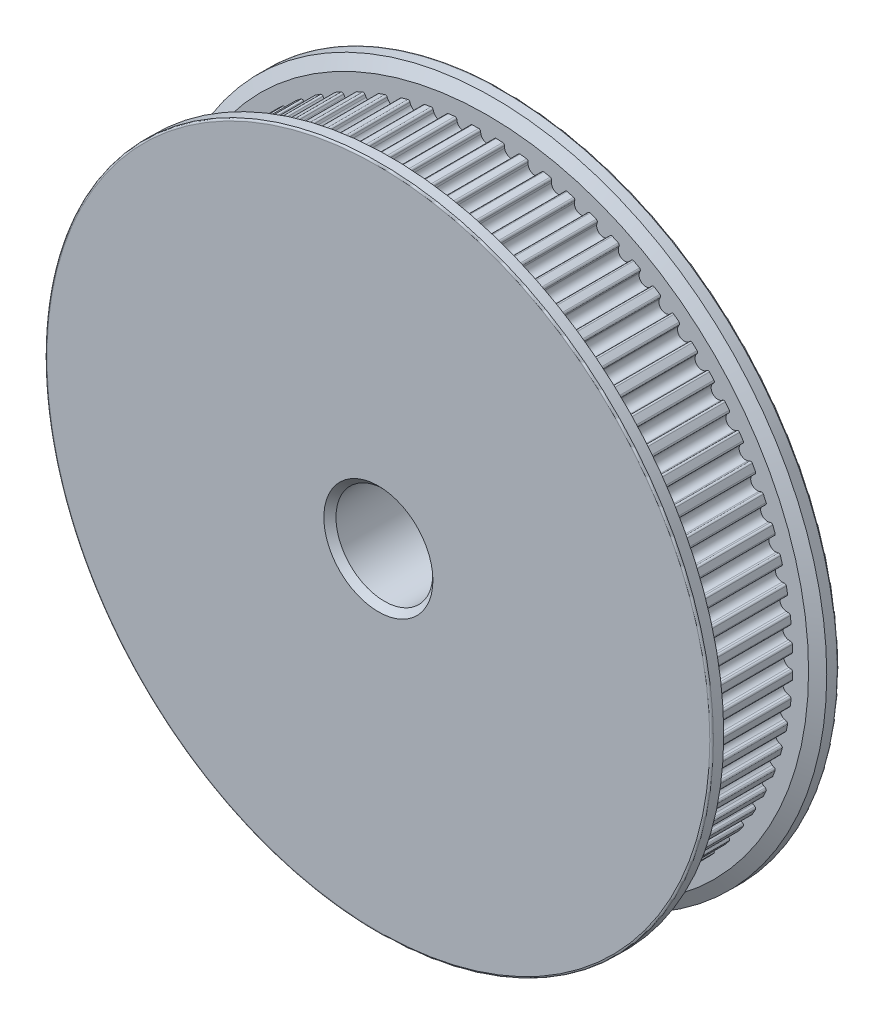
SolidWorks part; units mm, degrees
ref_plane "Front Plane" through (0, 0, 0) normal (0, 0, 1) x (1, 0, 0)
ref_plane "Top Plane" through (0, 0, 0) normal (0, 1, 0) x (1, 0, 0)
ref_plane "Right Plane" through (0, 0, 0) normal (1, 0, 0) x (0, 0, -1)
sketch "Sketch1" plane through (0, 0, 0) normal (0, 0, 1) x (1, 0, 0)
  circle A0 centre (0, 0) radius 19
  dimension "D1" = 38
extrude "Boss-Extrude1" add sketch "Sketch1" along normal blind 10
sketch "Sketch2" plane through (0, 0, 10) normal (0, 0, 1) x (1, 0, 0)
  circle A0 centre (0, 0) radius 27.5
  dimension "D1" = 55
extrude "Boss-Extrude2" add sketch "Sketch2" along normal blind 1.5 contours A0
sketch "Sketch3" plane through (0, 0, 11.5) normal (0, 0, 1) x (1, 0, 0)
  circle A0 centre (0, 0) radius 25.2
  dimension "D1" = 50.4
extrude "Boss-Extrude3" add sketch "Sketch3" along normal blind 7.5
sketch "Sketch4" plane through (0, 0, 19) normal (0, 0, 1) x (1, 0, 0)
  circle A0 centre (0, 0) radius 27.5
extrude "Boss-Extrude4" add sketch "Sketch4" along normal blind 1.5
sketch "Sketch5" plane through (0, 0, 11.5) normal (0, 0, 1) x (1, 0, 0)
  line L0 (0, 0) -> (38.9808, 0) construction
  line L1 (25.1897, 0.7199) -> (25.7855, 0.7199)
  line L2 (25.7855, 0.7199) -> (25.7855, -0.7199)
  line L3 (25.7855, -0.7199) -> (25.1897, -0.7199)
  line L4 (25.1685, -1.2587) -> (25.7625, -1.3054)
  line L5 (25.7625, -1.3054) -> (25.6496, -2.7408)
  line L6 (25.6496, -2.7408) -> (25.0556, -2.694)
  line L7 (24.9922, -3.2295) -> (25.5807, -3.3227)
  line L8 (25.5807, -3.3227) -> (25.3555, -4.7448)
  line L9 (25.3555, -4.7448) -> (24.767, -4.6516)
  line L10 (24.6618, -5.1804) -> (25.2411, -5.3195)
  line L11 (25.2411, -5.3195) -> (24.905, -6.7195)
  line L12 (24.905, -6.7195) -> (24.3257, -6.5804)
  line L13 (24.1793, -7.0994) -> (24.746, -7.2835)
  line L14 (24.746, -7.2835) -> (24.301, -8.6528)
  line L15 (24.301, -8.6528) -> (23.7344, -8.4687)
  line L16 (23.5477, -8.9746) -> (24.0982, -9.2026)
  line L17 (24.0982, -9.2026) -> (23.5472, -10.5328)
  line L18 (23.5472, -10.5328) -> (22.9968, -10.3048)
  line L19 (22.771, -10.7945) -> (23.3019, -11.065)
  line L20 (23.3019, -11.065) -> (22.6483, -12.3478)
  line L21 (22.6483, -12.3478) -> (22.1174, -12.0773)
  line L22 (21.8539, -12.5478) -> (22.3619, -12.8591)
  line L23 (22.3619, -12.8591) -> (21.6096, -14.0867)
  line L24 (21.6096, -14.0867) -> (21.1016, -13.7754)
  line L25 (20.802, -14.2237) -> (21.2841, -14.574)
  line L26 (21.2841, -14.574) -> (20.4378, -15.7388)
  line L27 (20.4378, -15.7388) -> (19.9558, -15.3885)
  line L28 (19.6219, -15.812) -> (20.075, -16.199)
  line L29 (20.075, -16.199) -> (19.1399, -17.2938)
  line L30 (19.1399, -17.2938) -> (18.6869, -16.9068)
  line L31 (18.3209, -17.3028) -> (18.7422, -17.7241)
  line L32 (18.7422, -17.7241) -> (17.7241, -18.7422)
  line L33 (17.7241, -18.7422) -> (17.3028, -18.3209)
  line L34 (16.9068, -18.6869) -> (17.2938, -19.1399)
  line L35 (17.2938, -19.1399) -> (16.199, -20.075)
  line L36 (16.199, -20.075) -> (15.812, -19.6219)
  line L37 (15.3885, -19.9558) -> (15.7388, -20.4378)
  line L38 (15.7388, -20.4378) -> (14.574, -21.2841)
  line L39 (14.574, -21.2841) -> (14.2237, -20.802)
  line L40 (13.7754, -21.1016) -> (14.0867, -21.6096)
  line L41 (14.0867, -21.6096) -> (12.8591, -22.3619)
  line L42 (12.8591, -22.3619) -> (12.5478, -21.8539)
  line L43 (12.0773, -22.1174) -> (12.3478, -22.6483)
  line L44 (12.3478, -22.6483) -> (11.065, -23.3019)
  line L45 (11.065, -23.3019) -> (10.7945, -22.771)
  line L46 (10.3048, -22.9968) -> (10.5328, -23.5472)
  line L47 (10.5328, -23.5472) -> (9.2026, -24.0982)
  line L48 (9.2026, -24.0982) -> (8.9746, -23.5477)
  line L49 (8.4687, -23.7344) -> (8.6528, -24.301)
  line L50 (8.6528, -24.301) -> (7.2835, -24.746)
  line L51 (7.2835, -24.746) -> (7.0994, -24.1793)
  line L52 (6.5804, -24.3257) -> (6.7195, -24.905)
  line L53 (6.7195, -24.905) -> (5.3195, -25.2411)
  line L54 (5.3195, -25.2411) -> (5.1804, -24.6618)
  line L55 (4.6516, -24.767) -> (4.7448, -25.3555)
  line L56 (4.7448, -25.3555) -> (3.3227, -25.5807)
  line L57 (3.3227, -25.5807) -> (3.2295, -24.9922)
  line L58 (2.694, -25.0556) -> (2.7408, -25.6496)
  line L59 (2.7408, -25.6496) -> (1.3054, -25.7625)
  line L60 (1.3054, -25.7625) -> (1.2587, -25.1685)
  line L61 (0.7199, -25.1897) -> (0.7199, -25.7855)
  line L62 (0.7199, -25.7855) -> (-0.7199, -25.7855)
  line L63 (-0.7199, -25.7855) -> (-0.7199, -25.1897)
  line L64 (-1.2587, -25.1685) -> (-1.3054, -25.7625)
  line L65 (-1.3054, -25.7625) -> (-2.7408, -25.6496)
  line L66 (-2.7408, -25.6496) -> (-2.694, -25.0556)
  line L67 (-3.2295, -24.9922) -> (-3.3227, -25.5807)
  line L68 (-3.3227, -25.5807) -> (-4.7448, -25.3555)
  line L69 (-4.7448, -25.3555) -> (-4.6516, -24.767)
  line L70 (-5.1804, -24.6618) -> (-5.3195, -25.2411)
  line L71 (-5.3195, -25.2411) -> (-6.7195, -24.905)
  line L72 (-6.7195, -24.905) -> (-6.5804, -24.3257)
  line L73 (-7.0994, -24.1793) -> (-7.2835, -24.746)
  line L74 (-7.2835, -24.746) -> (-8.6528, -24.301)
  line L75 (-8.6528, -24.301) -> (-8.4687, -23.7344)
  line L76 (-8.9746, -23.5477) -> (-9.2026, -24.0982)
  line L77 (-9.2026, -24.0982) -> (-10.5328, -23.5472)
  line L78 (-10.5328, -23.5472) -> (-10.3048, -22.9968)
  line L79 (-10.7945, -22.771) -> (-11.065, -23.3019)
  line L80 (-11.065, -23.3019) -> (-12.3478, -22.6483)
  line L81 (-12.3478, -22.6483) -> (-12.0773, -22.1174)
  line L82 (-12.5478, -21.8539) -> (-12.8591, -22.3619)
  line L83 (-12.8591, -22.3619) -> (-14.0867, -21.6096)
  line L84 (-14.0867, -21.6096) -> (-13.7754, -21.1016)
  line L85 (-14.2237, -20.802) -> (-14.574, -21.2841)
  line L86 (-14.574, -21.2841) -> (-15.7388, -20.4378)
  line L87 (-15.7388, -20.4378) -> (-15.3885, -19.9558)
  line L88 (-15.812, -19.6219) -> (-16.199, -20.075)
  line L89 (-16.199, -20.075) -> (-17.2938, -19.1399)
  line L90 (-17.2938, -19.1399) -> (-16.9068, -18.6869)
  line L91 (-17.3028, -18.3209) -> (-17.7241, -18.7422)
  line L92 (-17.7241, -18.7422) -> (-18.7422, -17.7241)
  line L93 (-18.7422, -17.7241) -> (-18.3209, -17.3028)
  line L94 (-18.6869, -16.9068) -> (-19.1399, -17.2938)
  line L95 (-19.1399, -17.2938) -> (-20.075, -16.199)
  line L96 (-20.075, -16.199) -> (-19.6219, -15.812)
  line L97 (-19.9558, -15.3885) -> (-20.4378, -15.7388)
  line L98 (-20.4378, -15.7388) -> (-21.2841, -14.574)
  line L99 (-21.2841, -14.574) -> (-20.802, -14.2237)
  line L100 (-21.1016, -13.7754) -> (-21.6096, -14.0867)
  line L101 (-21.6096, -14.0867) -> (-22.3619, -12.8591)
  line L102 (-22.3619, -12.8591) -> (-21.8539, -12.5478)
  line L103 (-22.1174, -12.0773) -> (-22.6483, -12.3478)
  line L104 (-22.6483, -12.3478) -> (-23.3019, -11.065)
  line L105 (-23.3019, -11.065) -> (-22.771, -10.7945)
  line L106 (-22.9968, -10.3048) -> (-23.5472, -10.5328)
  line L107 (-23.5472, -10.5328) -> (-24.0982, -9.2026)
  line L108 (-24.0982, -9.2026) -> (-23.5477, -8.9746)
  line L109 (-23.7344, -8.4687) -> (-24.301, -8.6528)
  line L110 (-24.301, -8.6528) -> (-24.746, -7.2835)
  line L111 (-24.746, -7.2835) -> (-24.1793, -7.0994)
  line L112 (-24.3257, -6.5804) -> (-24.905, -6.7195)
  line L113 (-24.905, -6.7195) -> (-25.2411, -5.3195)
  line L114 (-25.2411, -5.3195) -> (-24.6618, -5.1804)
  line L115 (-24.767, -4.6516) -> (-25.3555, -4.7448)
  line L116 (-25.3555, -4.7448) -> (-25.5807, -3.3227)
  line L117 (-25.5807, -3.3227) -> (-24.9922, -3.2295)
  line L118 (-25.0556, -2.694) -> (-25.6496, -2.7408)
  line L119 (-25.6496, -2.7408) -> (-25.7625, -1.3054)
  line L120 (-25.7625, -1.3054) -> (-25.1685, -1.2587)
  line L121 (-25.1897, -0.7199) -> (-25.7855, -0.7199)
  line L122 (-25.7855, -0.7199) -> (-25.7855, 0.7199)
  line L123 (-25.7855, 0.7199) -> (-25.1897, 0.7199)
  line L124 (-25.1685, 1.2587) -> (-25.7625, 1.3054)
  line L125 (-25.7625, 1.3054) -> (-25.6496, 2.7408)
  line L126 (-25.6496, 2.7408) -> (-25.0556, 2.694)
  line L127 (-24.9922, 3.2295) -> (-25.5807, 3.3227)
  line L128 (-25.5807, 3.3227) -> (-25.3555, 4.7448)
  line L129 (-25.3555, 4.7448) -> (-24.767, 4.6516)
  line L130 (-24.6618, 5.1804) -> (-25.2411, 5.3195)
  line L131 (-25.2411, 5.3195) -> (-24.905, 6.7195)
  line L132 (-24.905, 6.7195) -> (-24.3257, 6.5804)
  line L133 (-24.1793, 7.0994) -> (-24.746, 7.2835)
  line L134 (-24.746, 7.2835) -> (-24.301, 8.6528)
  line L135 (-24.301, 8.6528) -> (-23.7344, 8.4687)
  line L136 (-23.5477, 8.9746) -> (-24.0982, 9.2026)
  line L137 (-24.0982, 9.2026) -> (-23.5472, 10.5328)
  line L138 (-23.5472, 10.5328) -> (-22.9968, 10.3048)
  line L139 (-22.771, 10.7945) -> (-23.3019, 11.065)
  line L140 (-23.3019, 11.065) -> (-22.6483, 12.3478)
  line L141 (-22.6483, 12.3478) -> (-22.1174, 12.0773)
  line L142 (-21.8539, 12.5478) -> (-22.3619, 12.8591)
  line L143 (-22.3619, 12.8591) -> (-21.6096, 14.0867)
  line L144 (-21.6096, 14.0867) -> (-21.1016, 13.7754)
  line L145 (-20.802, 14.2237) -> (-21.2841, 14.574)
  line L146 (-21.2841, 14.574) -> (-20.4378, 15.7388)
  line L147 (-20.4378, 15.7388) -> (-19.9558, 15.3885)
  line L148 (-19.6219, 15.812) -> (-20.075, 16.199)
  line L149 (-20.075, 16.199) -> (-19.1399, 17.2938)
  line L150 (-19.1399, 17.2938) -> (-18.6869, 16.9068)
  line L151 (-18.3209, 17.3028) -> (-18.7422, 17.7241)
  line L152 (-18.7422, 17.7241) -> (-17.7241, 18.7422)
  line L153 (-17.7241, 18.7422) -> (-17.3028, 18.3209)
  line L154 (-16.9068, 18.6869) -> (-17.2938, 19.1399)
  line L155 (-17.2938, 19.1399) -> (-16.199, 20.075)
  line L156 (-16.199, 20.075) -> (-15.812, 19.6219)
  line L157 (-15.3885, 19.9558) -> (-15.7388, 20.4378)
  line L158 (-15.7388, 20.4378) -> (-14.574, 21.2841)
  line L159 (-14.574, 21.2841) -> (-14.2237, 20.802)
  line L160 (-13.7754, 21.1016) -> (-14.0867, 21.6096)
  line L161 (-14.0867, 21.6096) -> (-12.8591, 22.3619)
  line L162 (-12.8591, 22.3619) -> (-12.5478, 21.8539)
  line L163 (-12.0773, 22.1174) -> (-12.3478, 22.6483)
  line L164 (-12.3478, 22.6483) -> (-11.065, 23.3019)
  line L165 (-11.065, 23.3019) -> (-10.7945, 22.771)
  line L166 (-10.3048, 22.9968) -> (-10.5328, 23.5472)
  line L167 (-10.5328, 23.5472) -> (-9.2026, 24.0982)
  line L168 (-9.2026, 24.0982) -> (-8.9746, 23.5477)
  line L169 (-8.4687, 23.7344) -> (-8.6528, 24.301)
  line L170 (-8.6528, 24.301) -> (-7.2835, 24.746)
  line L171 (-7.2835, 24.746) -> (-7.0994, 24.1793)
  line L172 (-6.5804, 24.3257) -> (-6.7195, 24.905)
  line L173 (-6.7195, 24.905) -> (-5.3195, 25.2411)
  line L174 (-5.3195, 25.2411) -> (-5.1804, 24.6618)
  line L175 (-4.6516, 24.767) -> (-4.7448, 25.3555)
  line L176 (-4.7448, 25.3555) -> (-3.3227, 25.5807)
  line L177 (-3.3227, 25.5807) -> (-3.2295, 24.9922)
  line L178 (-2.694, 25.0556) -> (-2.7408, 25.6496)
  line L179 (-2.7408, 25.6496) -> (-1.3054, 25.7625)
  line L180 (-1.3054, 25.7625) -> (-1.2587, 25.1685)
  line L181 (-0.7199, 25.1897) -> (-0.7199, 25.7855)
  line L182 (-0.7199, 25.7855) -> (0.7199, 25.7855)
  line L183 (0.7199, 25.7855) -> (0.7199, 25.1897)
  line L184 (1.2587, 25.1685) -> (1.3054, 25.7625)
  line L185 (1.3054, 25.7625) -> (2.7408, 25.6496)
  line L186 (2.7408, 25.6496) -> (2.694, 25.0556)
  line L187 (3.2295, 24.9922) -> (3.3227, 25.5807)
  line L188 (3.3227, 25.5807) -> (4.7448, 25.3555)
  line L189 (4.7448, 25.3555) -> (4.6516, 24.767)
  line L190 (5.1804, 24.6618) -> (5.3195, 25.2411)
  line L191 (5.3195, 25.2411) -> (6.7195, 24.905)
  line L192 (6.7195, 24.905) -> (6.5804, 24.3257)
  line L193 (7.0994, 24.1793) -> (7.2835, 24.746)
  line L194 (7.2835, 24.746) -> (8.6528, 24.301)
  line L195 (8.6528, 24.301) -> (8.4687, 23.7344)
  line L196 (8.9746, 23.5477) -> (9.2026, 24.0982)
  line L197 (9.2026, 24.0982) -> (10.5328, 23.5472)
  line L198 (10.5328, 23.5472) -> (10.3048, 22.9968)
  line L199 (10.7945, 22.771) -> (11.065, 23.3019)
  line L200 (11.065, 23.3019) -> (12.3478, 22.6483)
  line L201 (12.3478, 22.6483) -> (12.0773, 22.1174)
  line L202 (12.5478, 21.8539) -> (12.8591, 22.3619)
  line L203 (12.8591, 22.3619) -> (14.0867, 21.6096)
  line L204 (14.0867, 21.6096) -> (13.7754, 21.1016)
  line L205 (14.2237, 20.802) -> (14.574, 21.2841)
  line L206 (14.574, 21.2841) -> (15.7388, 20.4378)
  line L207 (15.7388, 20.4378) -> (15.3885, 19.9558)
  line L208 (15.812, 19.6219) -> (16.199, 20.075)
  line L209 (16.199, 20.075) -> (17.2938, 19.1399)
  line L210 (17.2938, 19.1399) -> (16.9068, 18.6869)
  line L211 (17.3028, 18.3209) -> (17.7241, 18.7422)
  line L212 (17.7241, 18.7422) -> (18.7422, 17.7241)
  line L213 (18.7422, 17.7241) -> (18.3209, 17.3028)
  line L214 (18.6869, 16.9068) -> (19.1399, 17.2938)
  line L215 (19.1399, 17.2938) -> (20.075, 16.199)
  line L216 (20.075, 16.199) -> (19.6219, 15.812)
  line L217 (19.9558, 15.3885) -> (20.4378, 15.7388)
  line L218 (20.4378, 15.7388) -> (21.2841, 14.574)
  line L219 (21.2841, 14.574) -> (20.802, 14.2237)
  line L220 (21.1016, 13.7754) -> (21.6096, 14.0867)
  line L221 (21.6096, 14.0867) -> (22.3619, 12.8591)
  line L222 (22.3619, 12.8591) -> (21.8539, 12.5478)
  line L223 (22.1174, 12.0773) -> (22.6483, 12.3478)
  line L224 (22.6483, 12.3478) -> (23.3019, 11.065)
  line L225 (23.3019, 11.065) -> (22.771, 10.7945)
  line L226 (22.9968, 10.3048) -> (23.5472, 10.5328)
  line L227 (23.5472, 10.5328) -> (24.0982, 9.2026)
  line L228 (24.0982, 9.2026) -> (23.5477, 8.9746)
  line L229 (23.7344, 8.4687) -> (24.301, 8.6528)
  line L230 (24.301, 8.6528) -> (24.746, 7.2835)
  line L231 (24.746, 7.2835) -> (24.1793, 7.0994)
  line L232 (24.3257, 6.5804) -> (24.905, 6.7195)
  line L233 (24.905, 6.7195) -> (25.2411, 5.3195)
  line L234 (25.2411, 5.3195) -> (24.6618, 5.1804)
  line L235 (24.767, 4.6516) -> (25.3555, 4.7448)
  line L236 (25.3555, 4.7448) -> (25.5807, 3.3227)
  line L237 (25.5807, 3.3227) -> (24.9922, 3.2295)
  line L238 (25.0556, 2.694) -> (25.6496, 2.7408)
  line L239 (25.6496, 2.7408) -> (25.7625, 1.3054)
  line L240 (25.7625, 1.3054) -> (25.1685, 1.2587)
  circle A0 centre (0, 0) radius 25.45 construction
  circle A1 centre (0, 0) radius 25.2 construction
  arc A2 (24.8691, 0.5381) -> (24.8691, -0.5381) centre (25.005, 0) ccw
  arc A4 (24.8346, -1.4148) -> (24.7502, -2.4876) centre (24.9279, -1.9619) ccw
  arc A5 (25.0159, -1.4012) -> (25.1685, -1.2587) centre (25.0187, -1.2512) ccw
  arc A6 (25.0487, 0.5659) -> (25.1897, 0.7199) centre (25.0398, 0.7156) ccw
  arc A7 (25.0487, -0.5659) -> (25.1897, -0.7199) centre (25.0398, -0.7156) cw
  arc A8 (25.0487, 0.5659) -> (24.8691, 0.5381) centre (25.106, -0.4) ccw
  arc A9 (25.0487, -0.5659) -> (24.8691, -0.5381) centre (25.106, 0.4) cw
  arc A10 (24.9271, -2.5294) -> (25.0556, -2.694) centre (24.9064, -2.678) cw
  arc A11 (25.0159, -1.4012) -> (24.8346, -1.4148) centre (24.9973, -2.3686) ccw
  arc A12 (24.9271, -2.5294) -> (24.7502, -2.4876) centre (25.06, -1.571) cw
  circle A13 centre (0, 0) radius 25.45 construction
  circle A14 centre (0, 0) radius 25.2 construction
  arc A15 (24.6471, -3.3589) -> (24.4787, -4.4219) centre (24.6971, -3.9116) ccw
  arc A16 (24.8288, -3.3596) -> (24.9922, -3.2295) centre (24.8434, -3.2103) ccw
  arc A17 (24.6518, -4.4774) -> (24.767, -4.6516) centre (24.6196, -4.6239) cw
  arc A18 (24.8288, -3.3596) -> (24.6471, -3.3589) centre (24.7344, -4.3225) ccw
  arc A19 (24.6518, -4.4774) -> (24.4787, -4.4219) centre (24.8595, -3.5324) cw
  circle A20 centre (0, 0) radius 25.45 construction
  circle A21 centre (0, 0) radius 25.2 construction
  arc A22 (24.3076, -5.2823) -> (24.0563, -6.3288) centre (24.3141, -5.8373) ccw
  arc A23 (24.4887, -5.2973) -> (24.6618, -5.1804) centre (24.515, -5.1496) ccw
  arc A24 (24.2245, -6.3977) -> (24.3257, -6.5804) centre (24.1809, -6.5412) cw
  arc A25 (24.4887, -5.2973) -> (24.3076, -5.2823) centre (24.319, -6.2498) ccw
  arc A26 (24.2245, -6.3977) -> (24.0563, -6.3288) centre (24.5057, -5.4719) cw
  circle A27 centre (0, 0) radius 25.45 construction
  circle A28 centre (0, 0) radius 25.2 construction
  arc A29 (23.8182, -7.1732) -> (23.4856, -8.1967) centre (23.7812, -7.727) ccw
  arc A30 (23.9976, -7.2023) -> (24.1793, -7.0994) centre (24.0354, -7.0571) ccw
  arc A31 (23.6478, -8.2786) -> (23.7344, -8.4687) centre (23.5931, -8.4183) cw
  arc A32 (23.9976, -7.2023) -> (23.8182, -7.1732) centre (23.7537, -8.1386) ccw
  arc A33 (23.6478, -8.2786) -> (23.4856, -8.1967) centre (24.0009, -7.3778) cw
  circle A34 centre (0, 0) radius 25.45 construction
  circle A35 centre (0, 0) radius 25.2 construction
  arc A36 (23.182, -9.0198) -> (22.7701, -10.0141) centre (23.1016, -9.569) ccw
  arc A37 (23.3585, -9.0629) -> (23.5477, -8.9746) centre (23.4076, -8.9212) ccw
  arc A38 (22.9254, -10.1085) -> (22.9968, -10.3048) centre (22.8599, -10.2434) cw
  arc A39 (23.3585, -9.0629) -> (23.182, -9.0198) centre (23.0419, -9.9772) ccw
  arc A40 (22.9254, -10.1085) -> (22.7701, -10.0141) centre (23.348, -9.2381) cw
  circle A41 centre (0, 0) radius 25.45 construction
  circle A42 centre (0, 0) radius 25.2 construction
  arc A43 (22.4028, -10.8109) -> (21.9142, -11.7698) centre (22.2796, -11.352) ccw
  arc A44 (22.5754, -10.8677) -> (22.771, -10.7945) centre (22.6355, -10.7302) ccw
  arc A45 (22.0616, -11.876) -> (22.1174, -12.0773) centre (21.9857, -12.0054) cw
  arc A46 (22.5754, -10.8677) -> (22.4028, -10.8109) centre (22.188, -11.7543) ccw
  arc A47 (22.0616, -11.876) -> (21.9142, -11.7698) centre (22.5512, -11.0415) cw
  circle A48 centre (0, 0) radius 25.45 construction
  circle A49 centre (0, 0) radius 25.2 construction
  arc A50 (21.4855, -12.5353) -> (20.9232, -13.4529) centre (21.3203, -13.0651) ccw
  arc A51 (21.6532, -12.6054) -> (21.8539, -12.5478) centre (21.7238, -12.4731) ccw
  arc A52 (21.0618, -13.5704) -> (21.1016, -13.7754) centre (20.976, -13.6934) cw
  arc A53 (21.6532, -12.6054) -> (21.4855, -12.5353) centre (21.1974, -13.4589) ccw
  arc A54 (21.0618, -13.5704) -> (20.9232, -13.4529) centre (21.6154, -12.7768) cw
  circle A55 centre (0, 0) radius 25.45 construction
  circle A56 centre (0, 0) radius 25.2 construction
  arc A57 (20.4358, -14.1823) -> (19.8032, -15.053) centre (20.2295, -14.6976) ccw
  arc A58 (20.5974, -14.2654) -> (20.802, -14.2237) centre (20.6782, -14.1391) ccw
  arc A59 (19.9322, -15.181) -> (19.9558, -15.3885) centre (19.837, -15.2969) cw
  arc A60 (20.5974, -14.2654) -> (20.4358, -14.1823) centre (20.0761, -15.0806) ccw
  arc A61 (19.9322, -15.181) -> (19.8032, -15.053) centre (20.5463, -14.4334) cw
  circle A62 centre (0, 0) radius 25.45 construction
  circle A63 centre (0, 0) radius 25.2 construction
  arc A64 (19.2601, -15.742) -> (18.5611, -16.5603) centre (19.014, -16.2394) ccw
  arc A65 (19.4147, -15.8375) -> (19.6219, -15.812) centre (19.5051, -15.7179) ccw
  arc A66 (18.6797, -16.6981) -> (18.6869, -16.9068) centre (18.5757, -16.8062) cw
  arc A67 (19.4147, -15.8375) -> (19.2601, -15.742) centre (18.831, -16.6092) ccw
  arc A68 (18.6797, -16.6981) -> (18.5611, -16.5603) centre (19.3506, -16.0009) cw
  circle A69 centre (0, 0) radius 25.45 construction
  circle A70 centre (0, 0) radius 25.2 construction
  arc A71 (17.9656, -17.2046) -> (17.2046, -17.9656) centre (17.6812, -17.6812) ccw
  arc A72 (18.1122, -17.312) -> (18.3209, -17.3028) centre (18.2118, -17.1998) ccw
  arc A73 (17.312, -18.1122) -> (17.3028, -18.3209) centre (17.1998, -18.2118) cw
  arc A74 (18.1122, -17.312) -> (17.9656, -17.2046) centre (17.4698, -18.0355) ccw
  arc A75 (17.312, -18.1122) -> (17.2046, -17.9656) centre (18.0355, -17.4698) cw
  circle A76 centre (0, 0) radius 25.45 construction
  circle A77 centre (0, 0) radius 25.2 construction
  arc A78 (16.5603, -18.5611) -> (15.742, -19.2601) centre (16.2394, -19.014) ccw
  arc A79 (16.6981, -18.6797) -> (16.9068, -18.6869) centre (16.8062, -18.5757) ccw
  arc A80 (15.8375, -19.4147) -> (15.812, -19.6219) centre (15.7179, -19.5051) cw
  arc A81 (16.6981, -18.6797) -> (16.5603, -18.5611) centre (16.0009, -19.3506) ccw
  arc A82 (15.8375, -19.4147) -> (15.742, -19.2601) centre (16.6092, -18.831) cw
  circle A83 centre (0, 0) radius 25.45 construction
  circle A84 centre (0, 0) radius 25.2 construction
  arc A85 (15.053, -19.8032) -> (14.1823, -20.4358) centre (14.6976, -20.2295) ccw
  arc A86 (15.181, -19.9322) -> (15.3885, -19.9558) centre (15.2969, -19.837) ccw
  arc A87 (14.2654, -20.5974) -> (14.2237, -20.802) centre (14.1391, -20.6782) cw
  arc A88 (15.181, -19.9322) -> (15.053, -19.8032) centre (14.4334, -20.5463) ccw
  arc A89 (14.2654, -20.5974) -> (14.1823, -20.4358) centre (15.0806, -20.0761) cw
  circle A90 centre (0, 0) radius 25.45 construction
  circle A91 centre (0, 0) radius 25.2 construction
  arc A92 (13.4529, -20.9232) -> (12.5353, -21.4855) centre (13.0651, -21.3203) ccw
  arc A93 (13.5704, -21.0618) -> (13.7754, -21.1016) centre (13.6934, -20.976) ccw
  arc A94 (12.6054, -21.6532) -> (12.5478, -21.8539) centre (12.4731, -21.7238) cw
  arc A95 (13.5704, -21.0618) -> (13.4529, -20.9232) centre (12.7768, -21.6154) ccw
  arc A96 (12.6054, -21.6532) -> (12.5353, -21.4855) centre (13.4589, -21.1974) cw
  circle A97 centre (0, 0) radius 25.45 construction
  circle A98 centre (0, 0) radius 25.2 construction
  arc A99 (11.7698, -21.9142) -> (10.8109, -22.4028) centre (11.352, -22.2796) ccw
  arc A100 (11.876, -22.0616) -> (12.0773, -22.1174) centre (12.0054, -21.9857) ccw
  arc A101 (10.8677, -22.5754) -> (10.7945, -22.771) centre (10.7302, -22.6355) cw
  arc A102 (11.876, -22.0616) -> (11.7698, -21.9142) centre (11.0415, -22.5512) ccw
  arc A103 (10.8677, -22.5754) -> (10.8109, -22.4028) centre (11.7543, -22.188) cw
  circle A104 centre (0, 0) radius 25.45 construction
  circle A105 centre (0, 0) radius 25.2 construction
  arc A106 (10.0141, -22.7701) -> (9.0198, -23.182) centre (9.569, -23.1016) ccw
  arc A107 (10.1085, -22.9254) -> (10.3048, -22.9968) centre (10.2434, -22.8599) ccw
  arc A108 (9.0629, -23.3585) -> (8.9746, -23.5477) centre (8.9212, -23.4076) cw
  arc A109 (10.1085, -22.9254) -> (10.0141, -22.7701) centre (9.2381, -23.348) ccw
  arc A110 (9.0629, -23.3585) -> (9.0198, -23.182) centre (9.9772, -23.0419) cw
  circle A111 centre (0, 0) radius 25.45 construction
  circle A112 centre (0, 0) radius 25.2 construction
  arc A113 (8.1967, -23.4856) -> (7.1732, -23.8182) centre (7.727, -23.7812) ccw
  arc A114 (8.2786, -23.6478) -> (8.4687, -23.7344) centre (8.4183, -23.5931) ccw
  arc A115 (7.2023, -23.9976) -> (7.0994, -24.1793) centre (7.0571, -24.0354) cw
  arc A116 (8.2786, -23.6478) -> (8.1967, -23.4856) centre (7.3778, -24.0009) ccw
  arc A117 (7.2023, -23.9976) -> (7.1732, -23.8182) centre (8.1386, -23.7537) cw
  circle A118 centre (0, 0) radius 25.45 construction
  circle A119 centre (0, 0) radius 25.2 construction
  arc A120 (6.3288, -24.0563) -> (5.2823, -24.3076) centre (5.8373, -24.3141) ccw
  arc A121 (6.3977, -24.2245) -> (6.5804, -24.3257) centre (6.5412, -24.1809) ccw
  arc A122 (5.2973, -24.4887) -> (5.1804, -24.6618) centre (5.1496, -24.515) cw
  arc A123 (6.3977, -24.2245) -> (6.3288, -24.0563) centre (5.4719, -24.5057) ccw
  arc A124 (5.2973, -24.4887) -> (5.2823, -24.3076) centre (6.2498, -24.319) cw
  circle A125 centre (0, 0) radius 25.45 construction
  circle A126 centre (0, 0) radius 25.2 construction
  arc A127 (4.4219, -24.4787) -> (3.3589, -24.6471) centre (3.9116, -24.6971) ccw
  arc A128 (4.4774, -24.6518) -> (4.6516, -24.767) centre (4.6239, -24.6196) ccw
  arc A129 (3.3596, -24.8288) -> (3.2295, -24.9922) centre (3.2103, -24.8434) cw
  arc A130 (4.4774, -24.6518) -> (4.4219, -24.4787) centre (3.5324, -24.8595) ccw
  arc A131 (3.3596, -24.8288) -> (3.3589, -24.6471) centre (4.3225, -24.7344) cw
  circle A132 centre (0, 0) radius 25.45 construction
  circle A133 centre (0, 0) radius 25.2 construction
  arc A134 (2.4876, -24.7502) -> (1.4148, -24.8346) centre (1.9619, -24.9279) ccw
  arc A135 (2.5294, -24.9271) -> (2.694, -25.0556) centre (2.678, -24.9064) ccw
  arc A136 (1.4012, -25.0159) -> (1.2587, -25.1685) centre (1.2512, -25.0187) cw
  arc A137 (2.5294, -24.9271) -> (2.4876, -24.7502) centre (1.571, -25.06) ccw
  arc A138 (1.4012, -25.0159) -> (1.4148, -24.8346) centre (2.3686, -24.9973) cw
  circle A139 centre (0, 0) radius 25.45 construction
  circle A140 centre (0, 0) radius 25.2 construction
  arc A141 (0.5381, -24.8691) -> (-0.5381, -24.8691) centre (0, -25.005) ccw
  arc A142 (0.5659, -25.0487) -> (0.7199, -25.1897) centre (0.7156, -25.0398) ccw
  arc A143 (-0.5659, -25.0487) -> (-0.7199, -25.1897) centre (-0.7156, -25.0398) cw
  arc A144 (0.5659, -25.0487) -> (0.5381, -24.8691) centre (-0.4, -25.106) ccw
  arc A145 (-0.5659, -25.0487) -> (-0.5381, -24.8691) centre (0.4, -25.106) cw
  circle A146 centre (0, 0) radius 25.45 construction
  circle A147 centre (0, 0) radius 25.2 construction
  arc A148 (-1.4148, -24.8346) -> (-2.4876, -24.7502) centre (-1.9619, -24.9279) ccw
  arc A149 (-1.4012, -25.0159) -> (-1.2587, -25.1685) centre (-1.2512, -25.0187) ccw
  arc A150 (-2.5294, -24.9271) -> (-2.694, -25.0556) centre (-2.678, -24.9064) cw
  arc A151 (-1.4012, -25.0159) -> (-1.4148, -24.8346) centre (-2.3686, -24.9973) ccw
  arc A152 (-2.5294, -24.9271) -> (-2.4876, -24.7502) centre (-1.571, -25.06) cw
  circle A153 centre (0, 0) radius 25.45 construction
  circle A154 centre (0, 0) radius 25.2 construction
  arc A155 (-3.3589, -24.6471) -> (-4.4219, -24.4787) centre (-3.9116, -24.6971) ccw
  arc A156 (-3.3596, -24.8288) -> (-3.2295, -24.9922) centre (-3.2103, -24.8434) ccw
  arc A157 (-4.4774, -24.6518) -> (-4.6516, -24.767) centre (-4.6239, -24.6196) cw
  arc A158 (-3.3596, -24.8288) -> (-3.3589, -24.6471) centre (-4.3225, -24.7344) ccw
  arc A159 (-4.4774, -24.6518) -> (-4.4219, -24.4787) centre (-3.5324, -24.8595) cw
  circle A160 centre (0, 0) radius 25.45 construction
  circle A161 centre (0, 0) radius 25.2 construction
  arc A162 (-5.2823, -24.3076) -> (-6.3288, -24.0563) centre (-5.8373, -24.3141) ccw
  arc A163 (-5.2973, -24.4887) -> (-5.1804, -24.6618) centre (-5.1496, -24.515) ccw
  arc A164 (-6.3977, -24.2245) -> (-6.5804, -24.3257) centre (-6.5412, -24.1809) cw
  arc A165 (-5.2973, -24.4887) -> (-5.2823, -24.3076) centre (-6.2498, -24.319) ccw
  arc A166 (-6.3977, -24.2245) -> (-6.3288, -24.0563) centre (-5.4719, -24.5057) cw
  circle A167 centre (0, 0) radius 25.45 construction
  circle A168 centre (0, 0) radius 25.2 construction
  arc A169 (-7.1732, -23.8182) -> (-8.1967, -23.4856) centre (-7.727, -23.7812) ccw
  arc A170 (-7.2023, -23.9976) -> (-7.0994, -24.1793) centre (-7.0571, -24.0354) ccw
  arc A171 (-8.2786, -23.6478) -> (-8.4687, -23.7344) centre (-8.4183, -23.5931) cw
  arc A172 (-7.2023, -23.9976) -> (-7.1732, -23.8182) centre (-8.1386, -23.7537) ccw
  arc A173 (-8.2786, -23.6478) -> (-8.1967, -23.4856) centre (-7.3778, -24.0009) cw
  circle A174 centre (0, 0) radius 25.45 construction
  circle A175 centre (0, 0) radius 25.2 construction
  arc A176 (-9.0198, -23.182) -> (-10.0141, -22.7701) centre (-9.569, -23.1016) ccw
  arc A177 (-9.0629, -23.3585) -> (-8.9746, -23.5477) centre (-8.9212, -23.4076) ccw
  arc A178 (-10.1085, -22.9254) -> (-10.3048, -22.9968) centre (-10.2434, -22.8599) cw
  arc A179 (-9.0629, -23.3585) -> (-9.0198, -23.182) centre (-9.9772, -23.0419) ccw
  arc A180 (-10.1085, -22.9254) -> (-10.0141, -22.7701) centre (-9.2381, -23.348) cw
  circle A181 centre (0, 0) radius 25.45 construction
  circle A182 centre (0, 0) radius 25.2 construction
  arc A183 (-10.8109, -22.4028) -> (-11.7698, -21.9142) centre (-11.352, -22.2796) ccw
  arc A184 (-10.8677, -22.5754) -> (-10.7945, -22.771) centre (-10.7302, -22.6355) ccw
  arc A185 (-11.876, -22.0616) -> (-12.0773, -22.1174) centre (-12.0054, -21.9857) cw
  arc A186 (-10.8677, -22.5754) -> (-10.8109, -22.4028) centre (-11.7543, -22.188) ccw
  arc A187 (-11.876, -22.0616) -> (-11.7698, -21.9142) centre (-11.0415, -22.5512) cw
  circle A188 centre (0, 0) radius 25.45 construction
  circle A189 centre (0, 0) radius 25.2 construction
  arc A190 (-12.5353, -21.4855) -> (-13.4529, -20.9232) centre (-13.0651, -21.3203) ccw
  arc A191 (-12.6054, -21.6532) -> (-12.5478, -21.8539) centre (-12.4731, -21.7238) ccw
  arc A192 (-13.5704, -21.0618) -> (-13.7754, -21.1016) centre (-13.6934, -20.976) cw
  arc A193 (-12.6054, -21.6532) -> (-12.5353, -21.4855) centre (-13.4589, -21.1974) ccw
  arc A194 (-13.5704, -21.0618) -> (-13.4529, -20.9232) centre (-12.7768, -21.6154) cw
  circle A195 centre (0, 0) radius 25.45 construction
  circle A196 centre (0, 0) radius 25.2 construction
  arc A197 (-14.1823, -20.4358) -> (-15.053, -19.8032) centre (-14.6976, -20.2295) ccw
  arc A198 (-14.2654, -20.5974) -> (-14.2237, -20.802) centre (-14.1391, -20.6782) ccw
  arc A199 (-15.181, -19.9322) -> (-15.3885, -19.9558) centre (-15.2969, -19.837) cw
  arc A200 (-14.2654, -20.5974) -> (-14.1823, -20.4358) centre (-15.0806, -20.0761) ccw
  arc A201 (-15.181, -19.9322) -> (-15.053, -19.8032) centre (-14.4334, -20.5463) cw
  circle A202 centre (0, 0) radius 25.45 construction
  circle A203 centre (0, 0) radius 25.2 construction
  arc A204 (-15.742, -19.2601) -> (-16.5603, -18.5611) centre (-16.2394, -19.014) ccw
  arc A205 (-15.8375, -19.4147) -> (-15.812, -19.6219) centre (-15.7179, -19.5051) ccw
  arc A206 (-16.6981, -18.6797) -> (-16.9068, -18.6869) centre (-16.8062, -18.5757) cw
  arc A207 (-15.8375, -19.4147) -> (-15.742, -19.2601) centre (-16.6092, -18.831) ccw
  arc A208 (-16.6981, -18.6797) -> (-16.5603, -18.5611) centre (-16.0009, -19.3506) cw
  circle A209 centre (0, 0) radius 25.45 construction
  circle A210 centre (0, 0) radius 25.2 construction
  arc A211 (-17.2046, -17.9656) -> (-17.9656, -17.2046) centre (-17.6812, -17.6812) ccw
  arc A212 (-17.312, -18.1122) -> (-17.3028, -18.3209) centre (-17.1998, -18.2118) ccw
  arc A213 (-18.1122, -17.312) -> (-18.3209, -17.3028) centre (-18.2118, -17.1998) cw
  arc A214 (-17.312, -18.1122) -> (-17.2046, -17.9656) centre (-18.0355, -17.4698) ccw
  arc A215 (-18.1122, -17.312) -> (-17.9656, -17.2046) centre (-17.4698, -18.0355) cw
  circle A216 centre (0, 0) radius 25.45 construction
  circle A217 centre (0, 0) radius 25.2 construction
  arc A218 (-18.5611, -16.5603) -> (-19.2601, -15.742) centre (-19.014, -16.2394) ccw
  arc A219 (-18.6797, -16.6981) -> (-18.6869, -16.9068) centre (-18.5757, -16.8062) ccw
  arc A220 (-19.4147, -15.8375) -> (-19.6219, -15.812) centre (-19.5051, -15.7179) cw
  arc A221 (-18.6797, -16.6981) -> (-18.5611, -16.5603) centre (-19.3506, -16.0009) ccw
  arc A222 (-19.4147, -15.8375) -> (-19.2601, -15.742) centre (-18.831, -16.6092) cw
  circle A223 centre (0, 0) radius 25.45 construction
  circle A224 centre (0, 0) radius 25.2 construction
  arc A225 (-19.8032, -15.053) -> (-20.4358, -14.1823) centre (-20.2295, -14.6976) ccw
  arc A226 (-19.9322, -15.181) -> (-19.9558, -15.3885) centre (-19.837, -15.2969) ccw
  arc A227 (-20.5974, -14.2654) -> (-20.802, -14.2237) centre (-20.6782, -14.1391) cw
  arc A228 (-19.9322, -15.181) -> (-19.8032, -15.053) centre (-20.5463, -14.4334) ccw
  arc A229 (-20.5974, -14.2654) -> (-20.4358, -14.1823) centre (-20.0761, -15.0806) cw
  circle A230 centre (0, 0) radius 25.45 construction
  circle A231 centre (0, 0) radius 25.2 construction
  arc A232 (-20.9232, -13.4529) -> (-21.4855, -12.5353) centre (-21.3203, -13.0651) ccw
  arc A233 (-21.0618, -13.5704) -> (-21.1016, -13.7754) centre (-20.976, -13.6934) ccw
  arc A234 (-21.6532, -12.6054) -> (-21.8539, -12.5478) centre (-21.7238, -12.4731) cw
  arc A235 (-21.0618, -13.5704) -> (-20.9232, -13.4529) centre (-21.6154, -12.7768) ccw
  arc A236 (-21.6532, -12.6054) -> (-21.4855, -12.5353) centre (-21.1974, -13.4589) cw
  circle A237 centre (0, 0) radius 25.45 construction
  circle A238 centre (0, 0) radius 25.2 construction
  arc A239 (-21.9142, -11.7698) -> (-22.4028, -10.8109) centre (-22.2796, -11.352) ccw
  arc A240 (-22.0616, -11.876) -> (-22.1174, -12.0773) centre (-21.9857, -12.0054) ccw
  arc A241 (-22.5754, -10.8677) -> (-22.771, -10.7945) centre (-22.6355, -10.7302) cw
  arc A242 (-22.0616, -11.876) -> (-21.9142, -11.7698) centre (-22.5512, -11.0415) ccw
  arc A243 (-22.5754, -10.8677) -> (-22.4028, -10.8109) centre (-22.188, -11.7543) cw
  circle A244 centre (0, 0) radius 25.45 construction
  circle A245 centre (0, 0) radius 25.2 construction
  arc A246 (-22.7701, -10.0141) -> (-23.182, -9.0198) centre (-23.1016, -9.569) ccw
  arc A247 (-22.9254, -10.1085) -> (-22.9968, -10.3048) centre (-22.8599, -10.2434) ccw
  arc A248 (-23.3585, -9.0629) -> (-23.5477, -8.9746) centre (-23.4076, -8.9212) cw
  arc A249 (-22.9254, -10.1085) -> (-22.7701, -10.0141) centre (-23.348, -9.2381) ccw
  arc A250 (-23.3585, -9.0629) -> (-23.182, -9.0198) centre (-23.0419, -9.9772) cw
  circle A251 centre (0, 0) radius 25.45 construction
  circle A252 centre (0, 0) radius 25.2 construction
  arc A253 (-23.4856, -8.1967) -> (-23.8182, -7.1732) centre (-23.7812, -7.727) ccw
  arc A254 (-23.6478, -8.2786) -> (-23.7344, -8.4687) centre (-23.5931, -8.4183) ccw
  arc A255 (-23.9976, -7.2023) -> (-24.1793, -7.0994) centre (-24.0354, -7.0571) cw
  arc A256 (-23.6478, -8.2786) -> (-23.4856, -8.1967) centre (-24.0009, -7.3778) ccw
  arc A257 (-23.9976, -7.2023) -> (-23.8182, -7.1732) centre (-23.7537, -8.1386) cw
  circle A258 centre (0, 0) radius 25.45 construction
  circle A259 centre (0, 0) radius 25.2 construction
  arc A260 (-24.0563, -6.3288) -> (-24.3076, -5.2823) centre (-24.3141, -5.8373) ccw
  arc A261 (-24.2245, -6.3977) -> (-24.3257, -6.5804) centre (-24.1809, -6.5412) ccw
  arc A262 (-24.4887, -5.2973) -> (-24.6618, -5.1804) centre (-24.515, -5.1496) cw
  arc A263 (-24.2245, -6.3977) -> (-24.0563, -6.3288) centre (-24.5057, -5.4719) ccw
  arc A264 (-24.4887, -5.2973) -> (-24.3076, -5.2823) centre (-24.319, -6.2498) cw
  circle A265 centre (0, 0) radius 25.45 construction
  circle A266 centre (0, 0) radius 25.2 construction
  arc A267 (-24.4787, -4.4219) -> (-24.6471, -3.3589) centre (-24.6971, -3.9116) ccw
  arc A268 (-24.6518, -4.4774) -> (-24.767, -4.6516) centre (-24.6196, -4.6239) ccw
  arc A269 (-24.8288, -3.3596) -> (-24.9922, -3.2295) centre (-24.8434, -3.2103) cw
  arc A270 (-24.6518, -4.4774) -> (-24.4787, -4.4219) centre (-24.8595, -3.5324) ccw
  arc A271 (-24.8288, -3.3596) -> (-24.6471, -3.3589) centre (-24.7344, -4.3225) cw
  circle A272 centre (0, 0) radius 25.45 construction
  circle A273 centre (0, 0) radius 25.2 construction
  arc A274 (-24.7502, -2.4876) -> (-24.8346, -1.4148) centre (-24.9279, -1.9619) ccw
  arc A275 (-24.9271, -2.5294) -> (-25.0556, -2.694) centre (-24.9064, -2.678) ccw
  arc A276 (-25.0159, -1.4012) -> (-25.1685, -1.2587) centre (-25.0187, -1.2512) cw
  arc A277 (-24.9271, -2.5294) -> (-24.7502, -2.4876) centre (-25.06, -1.571) ccw
  arc A278 (-25.0159, -1.4012) -> (-24.8346, -1.4148) centre (-24.9973, -2.3686) cw
  circle A279 centre (0, 0) radius 25.45 construction
  circle A280 centre (0, 0) radius 25.2 construction
  arc A281 (-24.8691, -0.5381) -> (-24.8691, 0.5381) centre (-25.005, 0) ccw
  arc A282 (-25.0487, -0.5659) -> (-25.1897, -0.7199) centre (-25.0398, -0.7156) ccw
  arc A283 (-25.0487, 0.5659) -> (-25.1897, 0.7199) centre (-25.0398, 0.7156) cw
  arc A284 (-25.0487, -0.5659) -> (-24.8691, -0.5381) centre (-25.106, 0.4) ccw
  arc A285 (-25.0487, 0.5659) -> (-24.8691, 0.5381) centre (-25.106, -0.4) cw
  circle A286 centre (0, 0) radius 25.45 construction
  circle A287 centre (0, 0) radius 25.2 construction
  arc A288 (-24.8346, 1.4148) -> (-24.7502, 2.4876) centre (-24.9279, 1.9619) ccw
  arc A289 (-25.0159, 1.4012) -> (-25.1685, 1.2587) centre (-25.0187, 1.2512) ccw
  arc A290 (-24.9271, 2.5294) -> (-25.0556, 2.694) centre (-24.9064, 2.678) cw
  arc A291 (-25.0159, 1.4012) -> (-24.8346, 1.4148) centre (-24.9973, 2.3686) ccw
  arc A292 (-24.9271, 2.5294) -> (-24.7502, 2.4876) centre (-25.06, 1.571) cw
  circle A293 centre (0, 0) radius 25.45 construction
  circle A294 centre (0, 0) radius 25.2 construction
  arc A295 (-24.6471, 3.3589) -> (-24.4787, 4.4219) centre (-24.6971, 3.9116) ccw
  arc A296 (-24.8288, 3.3596) -> (-24.9922, 3.2295) centre (-24.8434, 3.2103) ccw
  arc A297 (-24.6518, 4.4774) -> (-24.767, 4.6516) centre (-24.6196, 4.6239) cw
  arc A298 (-24.8288, 3.3596) -> (-24.6471, 3.3589) centre (-24.7344, 4.3225) ccw
  arc A299 (-24.6518, 4.4774) -> (-24.4787, 4.4219) centre (-24.8595, 3.5324) cw
  circle A300 centre (0, 0) radius 25.45 construction
  circle A301 centre (0, 0) radius 25.2 construction
  arc A302 (-24.3076, 5.2823) -> (-24.0563, 6.3288) centre (-24.3141, 5.8373) ccw
  arc A303 (-24.4887, 5.2973) -> (-24.6618, 5.1804) centre (-24.515, 5.1496) ccw
  arc A304 (-24.2245, 6.3977) -> (-24.3257, 6.5804) centre (-24.1809, 6.5412) cw
  arc A305 (-24.4887, 5.2973) -> (-24.3076, 5.2823) centre (-24.319, 6.2498) ccw
  arc A306 (-24.2245, 6.3977) -> (-24.0563, 6.3288) centre (-24.5057, 5.4719) cw
  circle A307 centre (0, 0) radius 25.45 construction
  circle A308 centre (0, 0) radius 25.2 construction
  arc A309 (-23.8182, 7.1732) -> (-23.4856, 8.1967) centre (-23.7812, 7.727) ccw
  arc A310 (-23.9976, 7.2023) -> (-24.1793, 7.0994) centre (-24.0354, 7.0571) ccw
  arc A311 (-23.6478, 8.2786) -> (-23.7344, 8.4687) centre (-23.5931, 8.4183) cw
  arc A312 (-23.9976, 7.2023) -> (-23.8182, 7.1732) centre (-23.7537, 8.1386) ccw
  arc A313 (-23.6478, 8.2786) -> (-23.4856, 8.1967) centre (-24.0009, 7.3778) cw
  circle A314 centre (0, 0) radius 25.45 construction
  circle A315 centre (0, 0) radius 25.2 construction
  arc A316 (-23.182, 9.0198) -> (-22.7701, 10.0141) centre (-23.1016, 9.569) ccw
  arc A317 (-23.3585, 9.0629) -> (-23.5477, 8.9746) centre (-23.4076, 8.9212) ccw
  arc A318 (-22.9254, 10.1085) -> (-22.9968, 10.3048) centre (-22.8599, 10.2434) cw
  arc A319 (-23.3585, 9.0629) -> (-23.182, 9.0198) centre (-23.0419, 9.9772) ccw
  arc A320 (-22.9254, 10.1085) -> (-22.7701, 10.0141) centre (-23.348, 9.2381) cw
  circle A321 centre (0, 0) radius 25.45 construction
  circle A322 centre (0, 0) radius 25.2 construction
  arc A323 (-22.4028, 10.8109) -> (-21.9142, 11.7698) centre (-22.2796, 11.352) ccw
  arc A324 (-22.5754, 10.8677) -> (-22.771, 10.7945) centre (-22.6355, 10.7302) ccw
  arc A325 (-22.0616, 11.876) -> (-22.1174, 12.0773) centre (-21.9857, 12.0054) cw
  arc A326 (-22.5754, 10.8677) -> (-22.4028, 10.8109) centre (-22.188, 11.7543) ccw
  arc A327 (-22.0616, 11.876) -> (-21.9142, 11.7698) centre (-22.5512, 11.0415) cw
  circle A328 centre (0, 0) radius 25.45 construction
  circle A329 centre (0, 0) radius 25.2 construction
  arc A330 (-21.4855, 12.5353) -> (-20.9232, 13.4529) centre (-21.3203, 13.0651) ccw
  arc A331 (-21.6532, 12.6054) -> (-21.8539, 12.5478) centre (-21.7238, 12.4731) ccw
  arc A332 (-21.0618, 13.5704) -> (-21.1016, 13.7754) centre (-20.976, 13.6934) cw
  arc A333 (-21.6532, 12.6054) -> (-21.4855, 12.5353) centre (-21.1974, 13.4589) ccw
  arc A334 (-21.0618, 13.5704) -> (-20.9232, 13.4529) centre (-21.6154, 12.7768) cw
  circle A335 centre (0, 0) radius 25.45 construction
  circle A336 centre (0, 0) radius 25.2 construction
  arc A337 (-20.4358, 14.1823) -> (-19.8032, 15.053) centre (-20.2295, 14.6976) ccw
  arc A338 (-20.5974, 14.2654) -> (-20.802, 14.2237) centre (-20.6782, 14.1391) ccw
  arc A339 (-19.9322, 15.181) -> (-19.9558, 15.3885) centre (-19.837, 15.2969) cw
  arc A340 (-20.5974, 14.2654) -> (-20.4358, 14.1823) centre (-20.0761, 15.0806) ccw
  arc A341 (-19.9322, 15.181) -> (-19.8032, 15.053) centre (-20.5463, 14.4334) cw
  circle A342 centre (0, 0) radius 25.45 construction
  circle A343 centre (0, 0) radius 25.2 construction
  arc A344 (-19.2601, 15.742) -> (-18.5611, 16.5603) centre (-19.014, 16.2394) ccw
  arc A345 (-19.4147, 15.8375) -> (-19.6219, 15.812) centre (-19.5051, 15.7179) ccw
  arc A346 (-18.6797, 16.6981) -> (-18.6869, 16.9068) centre (-18.5757, 16.8062) cw
  arc A347 (-19.4147, 15.8375) -> (-19.2601, 15.742) centre (-18.831, 16.6092) ccw
  arc A348 (-18.6797, 16.6981) -> (-18.5611, 16.5603) centre (-19.3506, 16.0009) cw
  circle A349 centre (0, 0) radius 25.45 construction
  circle A350 centre (0, 0) radius 25.2 construction
  arc A351 (-17.9656, 17.2046) -> (-17.2046, 17.9656) centre (-17.6812, 17.6812) ccw
  arc A352 (-18.1122, 17.312) -> (-18.3209, 17.3028) centre (-18.2118, 17.1998) ccw
  arc A353 (-17.312, 18.1122) -> (-17.3028, 18.3209) centre (-17.1998, 18.2118) cw
  arc A354 (-18.1122, 17.312) -> (-17.9656, 17.2046) centre (-17.4698, 18.0355) ccw
  arc A355 (-17.312, 18.1122) -> (-17.2046, 17.9656) centre (-18.0355, 17.4698) cw
  circle A356 centre (0, 0) radius 25.45 construction
  circle A357 centre (0, 0) radius 25.2 construction
  arc A358 (-16.5603, 18.5611) -> (-15.742, 19.2601) centre (-16.2394, 19.014) ccw
  arc A359 (-16.6981, 18.6797) -> (-16.9068, 18.6869) centre (-16.8062, 18.5757) ccw
  arc A360 (-15.8375, 19.4147) -> (-15.812, 19.6219) centre (-15.7179, 19.5051) cw
  arc A361 (-16.6981, 18.6797) -> (-16.5603, 18.5611) centre (-16.0009, 19.3506) ccw
  arc A362 (-15.8375, 19.4147) -> (-15.742, 19.2601) centre (-16.6092, 18.831) cw
  circle A363 centre (0, 0) radius 25.45 construction
  circle A364 centre (0, 0) radius 25.2 construction
  arc A365 (-15.053, 19.8032) -> (-14.1823, 20.4358) centre (-14.6976, 20.2295) ccw
  arc A366 (-15.181, 19.9322) -> (-15.3885, 19.9558) centre (-15.2969, 19.837) ccw
  arc A367 (-14.2654, 20.5974) -> (-14.2237, 20.802) centre (-14.1391, 20.6782) cw
  arc A368 (-15.181, 19.9322) -> (-15.053, 19.8032) centre (-14.4334, 20.5463) ccw
  arc A369 (-14.2654, 20.5974) -> (-14.1823, 20.4358) centre (-15.0806, 20.0761) cw
  circle A370 centre (0, 0) radius 25.45 construction
  circle A371 centre (0, 0) radius 25.2 construction
  arc A372 (-13.4529, 20.9232) -> (-12.5353, 21.4855) centre (-13.0651, 21.3203) ccw
  arc A373 (-13.5704, 21.0618) -> (-13.7754, 21.1016) centre (-13.6934, 20.976) ccw
  arc A374 (-12.6054, 21.6532) -> (-12.5478, 21.8539) centre (-12.4731, 21.7238) cw
  arc A375 (-13.5704, 21.0618) -> (-13.4529, 20.9232) centre (-12.7768, 21.6154) ccw
  arc A376 (-12.6054, 21.6532) -> (-12.5353, 21.4855) centre (-13.4589, 21.1974) cw
  circle A377 centre (0, 0) radius 25.45 construction
  circle A378 centre (0, 0) radius 25.2 construction
  arc A379 (-11.7698, 21.9142) -> (-10.8109, 22.4028) centre (-11.352, 22.2796) ccw
  arc A380 (-11.876, 22.0616) -> (-12.0773, 22.1174) centre (-12.0054, 21.9857) ccw
  arc A381 (-10.8677, 22.5754) -> (-10.7945, 22.771) centre (-10.7302, 22.6355) cw
  arc A382 (-11.876, 22.0616) -> (-11.7698, 21.9142) centre (-11.0415, 22.5512) ccw
  arc A383 (-10.8677, 22.5754) -> (-10.8109, 22.4028) centre (-11.7543, 22.188) cw
  circle A384 centre (0, 0) radius 25.45 construction
  circle A385 centre (0, 0) radius 25.2 construction
  arc A386 (-10.0141, 22.7701) -> (-9.0198, 23.182) centre (-9.569, 23.1016) ccw
  arc A387 (-10.1085, 22.9254) -> (-10.3048, 22.9968) centre (-10.2434, 22.8599) ccw
  arc A388 (-9.0629, 23.3585) -> (-8.9746, 23.5477) centre (-8.9212, 23.4076) cw
  arc A389 (-10.1085, 22.9254) -> (-10.0141, 22.7701) centre (-9.2381, 23.348) ccw
  arc A390 (-9.0629, 23.3585) -> (-9.0198, 23.182) centre (-9.9772, 23.0419) cw
  circle A391 centre (0, 0) radius 25.45 construction
  circle A392 centre (0, 0) radius 25.2 construction
  arc A393 (-8.1967, 23.4856) -> (-7.1732, 23.8182) centre (-7.727, 23.7812) ccw
  arc A394 (-8.2786, 23.6478) -> (-8.4687, 23.7344) centre (-8.4183, 23.5931) ccw
  arc A395 (-7.2023, 23.9976) -> (-7.0994, 24.1793) centre (-7.0571, 24.0354) cw
  arc A396 (-8.2786, 23.6478) -> (-8.1967, 23.4856) centre (-7.3778, 24.0009) ccw
  arc A397 (-7.2023, 23.9976) -> (-7.1732, 23.8182) centre (-8.1386, 23.7537) cw
  circle A398 centre (0, 0) radius 25.45 construction
  circle A399 centre (0, 0) radius 25.2 construction
  arc A400 (-6.3288, 24.0563) -> (-5.2823, 24.3076) centre (-5.8373, 24.3141) ccw
  arc A401 (-6.3977, 24.2245) -> (-6.5804, 24.3257) centre (-6.5412, 24.1809) ccw
  arc A402 (-5.2973, 24.4887) -> (-5.1804, 24.6618) centre (-5.1496, 24.515) cw
  arc A403 (-6.3977, 24.2245) -> (-6.3288, 24.0563) centre (-5.4719, 24.5057) ccw
  arc A404 (-5.2973, 24.4887) -> (-5.2823, 24.3076) centre (-6.2498, 24.319) cw
  circle A405 centre (0, 0) radius 25.45 construction
  circle A406 centre (0, 0) radius 25.2 construction
  arc A407 (-4.4219, 24.4787) -> (-3.3589, 24.6471) centre (-3.9116, 24.6971) ccw
  arc A408 (-4.4774, 24.6518) -> (-4.6516, 24.767) centre (-4.6239, 24.6196) ccw
  arc A409 (-3.3596, 24.8288) -> (-3.2295, 24.9922) centre (-3.2103, 24.8434) cw
  arc A410 (-4.4774, 24.6518) -> (-4.4219, 24.4787) centre (-3.5324, 24.8595) ccw
  arc A411 (-3.3596, 24.8288) -> (-3.3589, 24.6471) centre (-4.3225, 24.7344) cw
  circle A412 centre (0, 0) radius 25.45 construction
  circle A413 centre (0, 0) radius 25.2 construction
  arc A414 (-2.4876, 24.7502) -> (-1.4148, 24.8346) centre (-1.9619, 24.9279) ccw
  arc A415 (-2.5294, 24.9271) -> (-2.694, 25.0556) centre (-2.678, 24.9064) ccw
  arc A416 (-1.4012, 25.0159) -> (-1.2587, 25.1685) centre (-1.2512, 25.0187) cw
  arc A417 (-2.5294, 24.9271) -> (-2.4876, 24.7502) centre (-1.571, 25.06) ccw
  arc A418 (-1.4012, 25.0159) -> (-1.4148, 24.8346) centre (-2.3686, 24.9973) cw
  circle A419 centre (0, 0) radius 25.45 construction
  circle A420 centre (0, 0) radius 25.2 construction
  arc A421 (-0.5381, 24.8691) -> (0.5381, 24.8691) centre (0, 25.005) ccw
  arc A422 (-0.5659, 25.0487) -> (-0.7199, 25.1897) centre (-0.7156, 25.0398) ccw
  arc A423 (0.5659, 25.0487) -> (0.7199, 25.1897) centre (0.7156, 25.0398) cw
  arc A424 (-0.5659, 25.0487) -> (-0.5381, 24.8691) centre (0.4, 25.106) ccw
  arc A425 (0.5659, 25.0487) -> (0.5381, 24.8691) centre (-0.4, 25.106) cw
  circle A426 centre (0, 0) radius 25.45 construction
  circle A427 centre (0, 0) radius 25.2 construction
  arc A428 (1.4148, 24.8346) -> (2.4876, 24.7502) centre (1.9619, 24.9279) ccw
  arc A429 (1.4012, 25.0159) -> (1.2587, 25.1685) centre (1.2512, 25.0187) ccw
  arc A430 (2.5294, 24.9271) -> (2.694, 25.0556) centre (2.678, 24.9064) cw
  arc A431 (1.4012, 25.0159) -> (1.4148, 24.8346) centre (2.3686, 24.9973) ccw
  arc A432 (2.5294, 24.9271) -> (2.4876, 24.7502) centre (1.571, 25.06) cw
  circle A433 centre (0, 0) radius 25.45 construction
  circle A434 centre (0, 0) radius 25.2 construction
  arc A435 (3.3589, 24.6471) -> (4.4219, 24.4787) centre (3.9116, 24.6971) ccw
  arc A436 (3.3596, 24.8288) -> (3.2295, 24.9922) centre (3.2103, 24.8434) ccw
  arc A437 (4.4774, 24.6518) -> (4.6516, 24.767) centre (4.6239, 24.6196) cw
  arc A438 (3.3596, 24.8288) -> (3.3589, 24.6471) centre (4.3225, 24.7344) ccw
  arc A439 (4.4774, 24.6518) -> (4.4219, 24.4787) centre (3.5324, 24.8595) cw
  circle A440 centre (0, 0) radius 25.45 construction
  circle A441 centre (0, 0) radius 25.2 construction
  arc A442 (5.2823, 24.3076) -> (6.3288, 24.0563) centre (5.8373, 24.3141) ccw
  arc A443 (5.2973, 24.4887) -> (5.1804, 24.6618) centre (5.1496, 24.515) ccw
  arc A444 (6.3977, 24.2245) -> (6.5804, 24.3257) centre (6.5412, 24.1809) cw
  arc A445 (5.2973, 24.4887) -> (5.2823, 24.3076) centre (6.2498, 24.319) ccw
  arc A446 (6.3977, 24.2245) -> (6.3288, 24.0563) centre (5.4719, 24.5057) cw
  circle A447 centre (0, 0) radius 25.45 construction
  circle A448 centre (0, 0) radius 25.2 construction
  arc A449 (7.1732, 23.8182) -> (8.1967, 23.4856) centre (7.727, 23.7812) ccw
  arc A450 (7.2023, 23.9976) -> (7.0994, 24.1793) centre (7.0571, 24.0354) ccw
  arc A451 (8.2786, 23.6478) -> (8.4687, 23.7344) centre (8.4183, 23.5931) cw
  arc A452 (7.2023, 23.9976) -> (7.1732, 23.8182) centre (8.1386, 23.7537) ccw
  arc A453 (8.2786, 23.6478) -> (8.1967, 23.4856) centre (7.3778, 24.0009) cw
  circle A454 centre (0, 0) radius 25.45 construction
  circle A455 centre (0, 0) radius 25.2 construction
  arc A456 (9.0198, 23.182) -> (10.0141, 22.7701) centre (9.569, 23.1016) ccw
  arc A457 (9.0629, 23.3585) -> (8.9746, 23.5477) centre (8.9212, 23.4076) ccw
  arc A458 (10.1085, 22.9254) -> (10.3048, 22.9968) centre (10.2434, 22.8599) cw
  arc A459 (9.0629, 23.3585) -> (9.0198, 23.182) centre (9.9772, 23.0419) ccw
  arc A460 (10.1085, 22.9254) -> (10.0141, 22.7701) centre (9.2381, 23.348) cw
  circle A461 centre (0, 0) radius 25.45 construction
  circle A462 centre (0, 0) radius 25.2 construction
  arc A463 (10.8109, 22.4028) -> (11.7698, 21.9142) centre (11.352, 22.2796) ccw
  arc A464 (10.8677, 22.5754) -> (10.7945, 22.771) centre (10.7302, 22.6355) ccw
  arc A465 (11.876, 22.0616) -> (12.0773, 22.1174) centre (12.0054, 21.9857) cw
  arc A466 (10.8677, 22.5754) -> (10.8109, 22.4028) centre (11.7543, 22.188) ccw
  arc A467 (11.876, 22.0616) -> (11.7698, 21.9142) centre (11.0415, 22.5512) cw
  circle A468 centre (0, 0) radius 25.45 construction
  circle A469 centre (0, 0) radius 25.2 construction
  arc A470 (12.5353, 21.4855) -> (13.4529, 20.9232) centre (13.0651, 21.3203) ccw
  arc A471 (12.6054, 21.6532) -> (12.5478, 21.8539) centre (12.4731, 21.7238) ccw
  arc A472 (13.5704, 21.0618) -> (13.7754, 21.1016) centre (13.6934, 20.976) cw
  arc A473 (12.6054, 21.6532) -> (12.5353, 21.4855) centre (13.4589, 21.1974) ccw
  arc A474 (13.5704, 21.0618) -> (13.4529, 20.9232) centre (12.7768, 21.6154) cw
  circle A475 centre (0, 0) radius 25.45 construction
  circle A476 centre (0, 0) radius 25.2 construction
  arc A477 (14.1823, 20.4358) -> (15.053, 19.8032) centre (14.6976, 20.2295) ccw
  arc A478 (14.2654, 20.5974) -> (14.2237, 20.802) centre (14.1391, 20.6782) ccw
  arc A479 (15.181, 19.9322) -> (15.3885, 19.9558) centre (15.2969, 19.837) cw
  arc A480 (14.2654, 20.5974) -> (14.1823, 20.4358) centre (15.0806, 20.0761) ccw
  arc A481 (15.181, 19.9322) -> (15.053, 19.8032) centre (14.4334, 20.5463) cw
  circle A482 centre (0, 0) radius 25.45 construction
  circle A483 centre (0, 0) radius 25.2 construction
  arc A484 (15.742, 19.2601) -> (16.5603, 18.5611) centre (16.2394, 19.014) ccw
  arc A485 (15.8375, 19.4147) -> (15.812, 19.6219) centre (15.7179, 19.5051) ccw
  arc A486 (16.6981, 18.6797) -> (16.9068, 18.6869) centre (16.8062, 18.5757) cw
  arc A487 (15.8375, 19.4147) -> (15.742, 19.2601) centre (16.6092, 18.831) ccw
  arc A488 (16.6981, 18.6797) -> (16.5603, 18.5611) centre (16.0009, 19.3506) cw
  circle A489 centre (0, 0) radius 25.45 construction
  circle A490 centre (0, 0) radius 25.2 construction
  arc A491 (17.2046, 17.9656) -> (17.9656, 17.2046) centre (17.6812, 17.6812) ccw
  arc A492 (17.312, 18.1122) -> (17.3028, 18.3209) centre (17.1998, 18.2118) ccw
  arc A493 (18.1122, 17.312) -> (18.3209, 17.3028) centre (18.2118, 17.1998) cw
  arc A494 (17.312, 18.1122) -> (17.2046, 17.9656) centre (18.0355, 17.4698) ccw
  arc A495 (18.1122, 17.312) -> (17.9656, 17.2046) centre (17.4698, 18.0355) cw
  circle A496 centre (0, 0) radius 25.45 construction
  circle A497 centre (0, 0) radius 25.2 construction
  arc A498 (18.5611, 16.5603) -> (19.2601, 15.742) centre (19.014, 16.2394) ccw
  arc A499 (18.6797, 16.6981) -> (18.6869, 16.9068) centre (18.5757, 16.8062) ccw
  arc A500 (19.4147, 15.8375) -> (19.6219, 15.812) centre (19.5051, 15.7179) cw
  arc A501 (18.6797, 16.6981) -> (18.5611, 16.5603) centre (19.3506, 16.0009) ccw
  arc A502 (19.4147, 15.8375) -> (19.2601, 15.742) centre (18.831, 16.6092) cw
  circle A503 centre (0, 0) radius 25.45 construction
  circle A504 centre (0, 0) radius 25.2 construction
  arc A505 (19.8032, 15.053) -> (20.4358, 14.1823) centre (20.2295, 14.6976) ccw
  arc A506 (19.9322, 15.181) -> (19.9558, 15.3885) centre (19.837, 15.2969) ccw
  arc A507 (20.5974, 14.2654) -> (20.802, 14.2237) centre (20.6782, 14.1391) cw
  arc A508 (19.9322, 15.181) -> (19.8032, 15.053) centre (20.5463, 14.4334) ccw
  arc A509 (20.5974, 14.2654) -> (20.4358, 14.1823) centre (20.0761, 15.0806) cw
  circle A510 centre (0, 0) radius 25.45 construction
  circle A511 centre (0, 0) radius 25.2 construction
  arc A512 (20.9232, 13.4529) -> (21.4855, 12.5353) centre (21.3203, 13.0651) ccw
  arc A513 (21.0618, 13.5704) -> (21.1016, 13.7754) centre (20.976, 13.6934) ccw
  arc A514 (21.6532, 12.6054) -> (21.8539, 12.5478) centre (21.7238, 12.4731) cw
  arc A515 (21.0618, 13.5704) -> (20.9232, 13.4529) centre (21.6154, 12.7768) ccw
  arc A516 (21.6532, 12.6054) -> (21.4855, 12.5353) centre (21.1974, 13.4589) cw
  circle A517 centre (0, 0) radius 25.45 construction
  circle A518 centre (0, 0) radius 25.2 construction
  arc A519 (21.9142, 11.7698) -> (22.4028, 10.8109) centre (22.2796, 11.352) ccw
  arc A520 (22.0616, 11.876) -> (22.1174, 12.0773) centre (21.9857, 12.0054) ccw
  arc A521 (22.5754, 10.8677) -> (22.771, 10.7945) centre (22.6355, 10.7302) cw
  arc A522 (22.0616, 11.876) -> (21.9142, 11.7698) centre (22.5512, 11.0415) ccw
  arc A523 (22.5754, 10.8677) -> (22.4028, 10.8109) centre (22.188, 11.7543) cw
  circle A524 centre (0, 0) radius 25.45 construction
  circle A525 centre (0, 0) radius 25.2 construction
  arc A526 (22.7701, 10.0141) -> (23.182, 9.0198) centre (23.1016, 9.569) ccw
  arc A527 (22.9254, 10.1085) -> (22.9968, 10.3048) centre (22.8599, 10.2434) ccw
  arc A528 (23.3585, 9.0629) -> (23.5477, 8.9746) centre (23.4076, 8.9212) cw
  arc A529 (22.9254, 10.1085) -> (22.7701, 10.0141) centre (23.348, 9.2381) ccw
  arc A530 (23.3585, 9.0629) -> (23.182, 9.0198) centre (23.0419, 9.9772) cw
  circle A531 centre (0, 0) radius 25.45 construction
  circle A532 centre (0, 0) radius 25.2 construction
  arc A533 (23.4856, 8.1967) -> (23.8182, 7.1732) centre (23.7812, 7.727) ccw
  arc A534 (23.6478, 8.2786) -> (23.7344, 8.4687) centre (23.5931, 8.4183) ccw
  arc A535 (23.9976, 7.2023) -> (24.1793, 7.0994) centre (24.0354, 7.0571) cw
  arc A536 (23.6478, 8.2786) -> (23.4856, 8.1967) centre (24.0009, 7.3778) ccw
  arc A537 (23.9976, 7.2023) -> (23.8182, 7.1732) centre (23.7537, 8.1386) cw
  circle A538 centre (0, 0) radius 25.45 construction
  circle A539 centre (0, 0) radius 25.2 construction
  arc A540 (24.0563, 6.3288) -> (24.3076, 5.2823) centre (24.3141, 5.8373) ccw
  arc A541 (24.2245, 6.3977) -> (24.3257, 6.5804) centre (24.1809, 6.5412) ccw
  arc A542 (24.4887, 5.2973) -> (24.6618, 5.1804) centre (24.515, 5.1496) cw
  arc A543 (24.2245, 6.3977) -> (24.0563, 6.3288) centre (24.5057, 5.4719) ccw
  arc A544 (24.4887, 5.2973) -> (24.3076, 5.2823) centre (24.319, 6.2498) cw
  circle A545 centre (0, 0) radius 25.45 construction
  circle A546 centre (0, 0) radius 25.2 construction
  arc A547 (24.4787, 4.4219) -> (24.6471, 3.3589) centre (24.6971, 3.9116) ccw
  arc A548 (24.6518, 4.4774) -> (24.767, 4.6516) centre (24.6196, 4.6239) ccw
  arc A549 (24.8288, 3.3596) -> (24.9922, 3.2295) centre (24.8434, 3.2103) cw
  arc A550 (24.6518, 4.4774) -> (24.4787, 4.4219) centre (24.8595, 3.5324) ccw
  arc A551 (24.8288, 3.3596) -> (24.6471, 3.3589) centre (24.7344, 4.3225) cw
  circle A552 centre (0, 0) radius 25.45 construction
  circle A553 centre (0, 0) radius 25.2 construction
  arc A554 (24.7502, 2.4876) -> (24.8346, 1.4148) centre (24.9279, 1.9619) ccw
  arc A555 (24.9271, 2.5294) -> (25.0556, 2.694) centre (24.9064, 2.678) ccw
  arc A556 (25.0159, 1.4012) -> (25.1685, 1.2587) centre (25.0187, 1.2512) cw
  arc A557 (24.9271, 2.5294) -> (24.7502, 2.4876) centre (25.06, 1.571) ccw
  arc A558 (25.0159, 1.4012) -> (24.8346, 1.4148) centre (24.9973, 2.3686) cw
  circle A559 centre (0, 0) radius 25.45 construction
  circle A560 centre (0, 0) radius 25.2 construction
  point P7 (25.106, -0.4)
  point P8 (19.4904, 0)
  point P9 (25.2, 0)
  point P27 (24.9973, -2.3686)
  point P28 (25.1223, -1.9772)
  point P44 (24.7344, -4.3225)
  point P45 (24.8897, -3.9421)
  point P61 (24.319, -6.2498)
  point P62 (24.5037, -5.8828)
  point P78 (23.7537, -8.1386)
  point P79 (23.9666, -7.7872)
  point P95 (23.0419, -9.9772)
  point P96 (23.2818, -9.6436)
  point P112 (22.188, -11.7543)
  point P113 (22.4534, -11.4406)
  point P129 (21.1974, -13.4589)
  point P130 (21.4865, -13.167)
  point P146 (20.0761, -15.0806)
  point P147 (20.3872, -14.8122)
  point P163 (18.831, -16.6092)
  point P164 (19.1622, -16.3661)
  point P180 (17.4698, -18.0355)
  point P181 (17.8191, -17.8191)
  point P197 (16.0009, -19.3506)
  point P198 (16.3661, -19.1622)
  point P214 (14.4334, -20.5463)
  point P215 (14.8122, -20.3872)
  point P231 (12.7768, -21.6154)
  point P232 (13.167, -21.4865)
  point P248 (11.0415, -22.5512)
  point P249 (11.4406, -22.4534)
  point P265 (9.2381, -23.348)
  point P266 (9.6436, -23.2818)
  point P282 (7.3778, -24.0009)
  point P283 (7.7872, -23.9666)
  point P299 (5.4719, -24.5057)
  point P300 (5.8828, -24.5037)
  point P316 (3.5324, -24.8595)
  point P317 (3.9421, -24.8897)
  point P333 (1.571, -25.06)
  point P334 (1.9772, -25.1223)
  point P350 (-0.4, -25.106)
  point P351 (0, -25.2)
  point P367 (-2.3686, -24.9973)
  point P368 (-1.9772, -25.1223)
  point P384 (-4.3225, -24.7344)
  point P385 (-3.9421, -24.8897)
  point P401 (-6.2498, -24.319)
  point P402 (-5.8828, -24.5037)
  point P418 (-8.1386, -23.7537)
  point P419 (-7.7872, -23.9666)
  point P435 (-9.9772, -23.0419)
  point P436 (-9.6436, -23.2818)
  point P452 (-11.7543, -22.188)
  point P453 (-11.4406, -22.4534)
  point P469 (-13.4589, -21.1974)
  point P470 (-13.167, -21.4865)
  point P486 (-15.0806, -20.0761)
  point P487 (-14.8122, -20.3872)
  point P503 (-16.6092, -18.831)
  point P504 (-16.3661, -19.1622)
  point P520 (-18.0355, -17.4698)
  point P521 (-17.8191, -17.8191)
  point P537 (-19.3506, -16.0009)
  point P538 (-19.1622, -16.3661)
  point P554 (-20.5463, -14.4334)
  point P555 (-20.3872, -14.8122)
  point P571 (-21.6154, -12.7768)
  point P572 (-21.4865, -13.167)
  point P588 (-22.5512, -11.0415)
  point P589 (-22.4534, -11.4406)
  point P605 (-23.348, -9.2381)
  point P606 (-23.2818, -9.6436)
  point P622 (-24.0009, -7.3778)
  point P623 (-23.9666, -7.7872)
  point P639 (-24.5057, -5.4719)
  point P640 (-24.5037, -5.8828)
  point P656 (-24.8595, -3.5324)
  point P657 (-24.8897, -3.9421)
  point P673 (-25.06, -1.571)
  point P674 (-25.1223, -1.9772)
  point P690 (-25.106, 0.4)
  point P691 (-25.2, 0)
  point P707 (-24.9973, 2.3686)
  point P708 (-25.1223, 1.9772)
  point P724 (-24.7344, 4.3225)
  point P725 (-24.8897, 3.9421)
  point P741 (-24.319, 6.2498)
  point P742 (-24.5037, 5.8828)
  point P758 (-23.7537, 8.1386)
  point P759 (-23.9666, 7.7872)
  point P775 (-23.0419, 9.9772)
  point P776 (-23.2818, 9.6436)
  point P792 (-22.188, 11.7543)
  point P793 (-22.4534, 11.4406)
  point P809 (-21.1974, 13.4589)
  point P810 (-21.4865, 13.167)
  point P826 (-20.0761, 15.0806)
  point P827 (-20.3872, 14.8122)
  point P843 (-18.831, 16.6092)
  point P844 (-19.1622, 16.3661)
  point P860 (-17.4698, 18.0355)
  point P861 (-17.8191, 17.8191)
  point P877 (-16.0009, 19.3506)
  point P878 (-16.3661, 19.1622)
  point P894 (-14.4334, 20.5463)
  point P895 (-14.8122, 20.3872)
  point P911 (-12.7768, 21.6154)
  point P912 (-13.167, 21.4865)
  point P928 (-11.0415, 22.5512)
  point P929 (-11.4406, 22.4534)
  point P945 (-9.2381, 23.348)
  point P946 (-9.6436, 23.2818)
  point P962 (-7.3778, 24.0009)
  point P963 (-7.7872, 23.9666)
  point P979 (-5.4719, 24.5057)
  point P980 (-5.8828, 24.5037)
  point P996 (-3.5324, 24.8595)
  point P997 (-3.9421, 24.8897)
  point P1013 (-1.571, 25.06)
  point P1014 (-1.9772, 25.1223)
  point P1030 (0.4, 25.106)
  point P1031 (0, 25.2)
  point P1047 (2.3686, 24.9973)
  point P1048 (1.9772, 25.1223)
  point P1064 (4.3225, 24.7344)
  point P1065 (3.9421, 24.8897)
  point P1081 (6.2498, 24.319)
  point P1082 (5.8828, 24.5037)
  point P1098 (8.1386, 23.7537)
  point P1099 (7.7872, 23.9666)
  point P1115 (9.9772, 23.0419)
  point P1116 (9.6436, 23.2818)
  point P1132 (11.7543, 22.188)
  point P1133 (11.4406, 22.4534)
  point P1149 (13.4589, 21.1974)
  point P1150 (13.167, 21.4865)
  point P1166 (15.0806, 20.0761)
  point P1167 (14.8122, 20.3872)
  point P1183 (16.6092, 18.831)
  point P1184 (16.3661, 19.1622)
  point P1200 (18.0355, 17.4698)
  point P1201 (17.8191, 17.8191)
  point P1217 (19.3506, 16.0009)
  point P1218 (19.1622, 16.3661)
  point P1234 (20.5463, 14.4334)
  point P1235 (20.3872, 14.8122)
  point P1251 (21.6154, 12.7768)
  point P1252 (21.4865, 13.167)
  point P1268 (22.5512, 11.0415)
  point P1269 (22.4534, 11.4406)
  point P1285 (23.348, 9.2381)
  point P1286 (23.2818, 9.6436)
  point P1302 (24.0009, 7.3778)
  point P1303 (23.9666, 7.7872)
  point P1319 (24.5057, 5.4719)
  point P1320 (24.5037, 5.8828)
  point P1336 (24.8595, 3.5324)
  point P1337 (24.8897, 3.9421)
  point P1353 (25.06, 1.571)
  point P1354 (25.1223, 1.9772)
  point P1367 (0, 0)
  dimension "D1" = 50.9
  dimension "D2" = 1.11
  dimension "D4" = 50.4
  dimension "D6" = 0.3
  dimension "D3" = 0.195
  dimension "D5" = 0.4
  dimension "D7" = 80
extrude "Cut-Extrude1" cut sketch "Sketch5" along normal blind 7.5
chamfer "Chamfer1" distance 0.5 distance2 1 1 edges at (27.5, 0, 11.5) first distance on face at (27.5, 0, 11.5)
chamfer "Chamfer2" distance 1 distance2 0.5 1 edges at (27.5, 0, 19) first distance on face at (0, 0, 19)
fillet "Fillet2" radius 0.15 2 edges at (27.5, 0, 20.5) (27.5, 0, 10)
sketch "Sketch6" plane through (0, 0, 0) normal (0, 0, -1) x (-1, 0, 0)
  circle A0 centre (0, 0) radius 19
extrude "Cut-Extrude2" cut sketch "Sketch6" against normal up to surface (10 mm away) up to face at (27.35, 0, 10)
sketch "Sketch11" plane through (0, 0, 10) normal (0, 0, -1) x (-1, 0, 0)
  circle A0 centre (0, 0) radius 17.5
  dimension "D1" = 35
extrude "Boss-Extrude5" add sketch "Sketch11" along normal blind 3.5
sketch "Sketch12" plane through (0, 0, 6.5) normal (0, 0, -1) x (-1, 0, 0)
  circle A0 centre (0, 0) radius 4
  dimension "D1" = 8
extrude "Cut-Extrude6" cut sketch "Sketch12" against normal up to surface (14 mm away) up to face at (27.35, 0, 20.5)
chamfer "Chamfer4" distance 0.5 angle 45 2 edges at (-4, 0, 6.5) (4, 0, 20.5)
